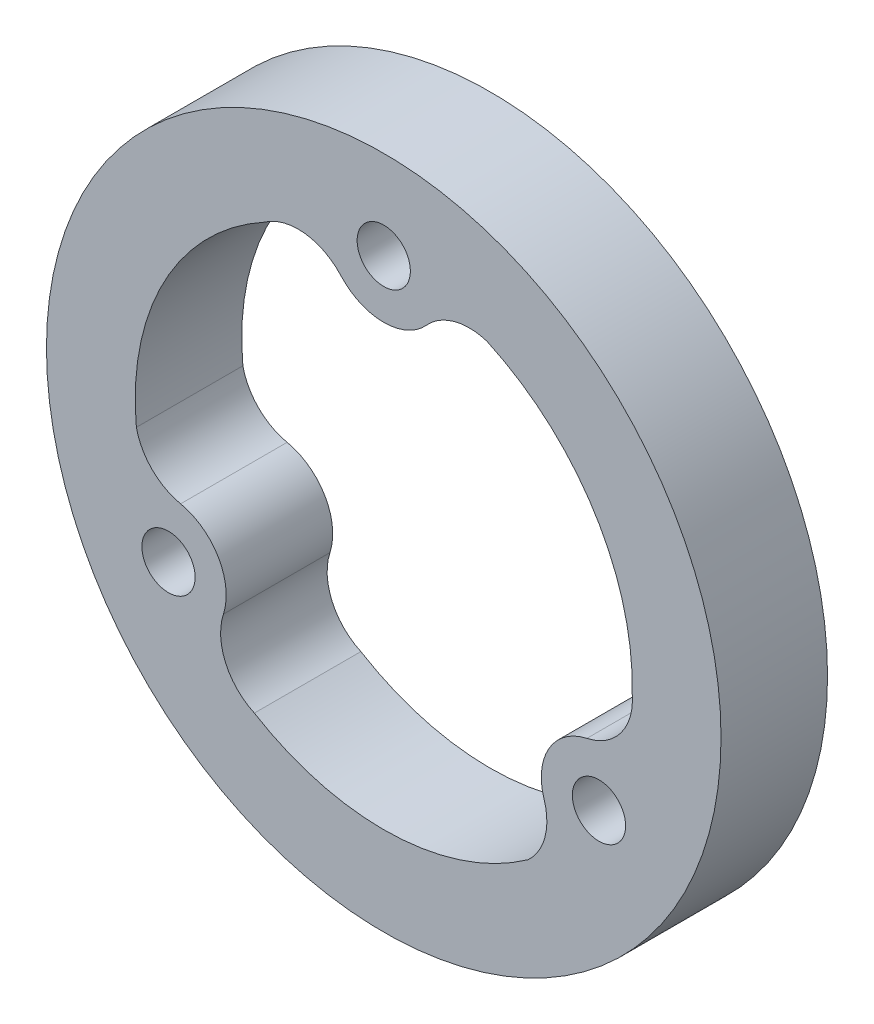
SolidWorks part; units mm, degrees
ref_plane "Plan de face" through (0, 0, 0) normal (0, 0, 1) x (1, 0, 0)
ref_plane "Plan de dessus" through (0, 0, 0) normal (0, 1, 0) x (1, 0, 0)
ref_plane "Plan de droite" through (0, 0, 0) normal (1, 0, 0) x (0, 0, -1)
sketch "Esquisse1" plane through (0, 0, 0) normal (0, 0, 1) x (1, 0, 0)
  line L0 (0, 14) -> (-12.125, -7.0011) construction
  line L1 (-12.125, -7.0011) -> (12.125, -7.0011) construction
  line L2 (12.125, -7.0011) -> (0, 14) construction
  circle A0 centre (0, 0) radius 19
  circle A2 centre (0, 14) radius 1.5
  arc A12 (-2.411, 11.8207) -> (2.411, 11.8207) centre (0, 14) ccw
  arc A16 (5.8094, 12.7378) -> (2.411, 11.8207) centre (4.8221, 9.6414) ccw
  arc A17 (-2.411, 11.8207) -> (-6.7074, 12.2887) centre (-4.8221, 9.6414) ccw
  arc A18 (-6.7074, 12.2887) -> (-13.9359, -1.3378) centre (0, 0) ccw
  arc A19 (8.1265, -11.4) -> (9.0315, -7.9984) centre (5.9386, -8.9967) ccw
  arc A20 (11.4425, -3.8223) -> (9.0315, -7.9984) centre (12.1244, -7) ccw
  arc A21 (11.4425, -3.8223) -> (13.996, -0.3356) centre (10.7607, -0.6447) ccw
  circle A22 centre (12.1244, -7) radius 1.5
  arc A23 (-13.9359, -1.3378) -> (-11.4425, -3.8223) centre (-10.7607, -0.6447) ccw
  arc A24 (-9.0315, -7.9984) -> (-11.4425, -3.8223) centre (-12.1244, -7) ccw
  arc A25 (-9.0315, -7.9984) -> (-7.2886, -11.9531) centre (-5.9386, -8.9967) ccw
  circle A26 centre (-12.1244, -7) radius 1.5
  arc A27 (-7.2886, -11.9531) -> (8.1265, -11.4) centre (0, 0) ccw
  arc A28 (13.996, -0.3356) -> (5.8094, 12.7378) centre (0, 0) ccw
  circle A29 centre (0, 14) radius 3.25 construction
  point P7 (0, 0)
  point P31 (0, 0)
  point P32 (0, 0)
  point P33 (0, 0)
  point P34 (0, 0)
  dimension "D1" = 38
  dimension "D2" = 3
  dimension "D3" = 3
  dimension "D4" = 6.5
  dimension "D5" = 14
  dimension "D8" = 14
  dimension "D9" = 3.25
  dimension "D10" = 14
  dimension "D11" = 3.25
  dimension "D12" = 24.25
  dimension "D13" = 24.25
  dimension "D6" = 60
  dimension "D7" = 60
  dimension "D14" = 10.78
  dimension "D15" = 10.78
extrude "Boss.-Extru.2" add sketch "Esquisse1" along normal blind 6
